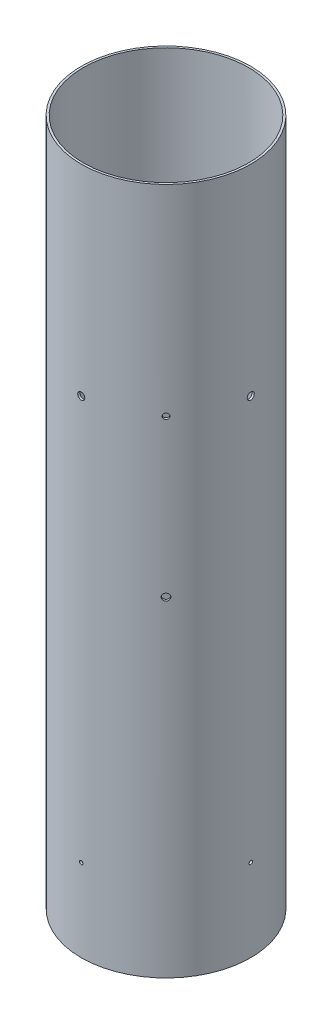
SolidWorks part; units mm, degrees
ref_plane "Front Plane" through (0, 0, 0) normal (0, 0, 1) x (1, 0, 0)
ref_plane "Top Plane" through (0, 0, 0) normal (0, 1, 0) x (1, 0, 0)
ref_plane "Right Plane" through (0, 0, 0) normal (1, 0, 0) x (0, 0, -1)
sketch "Sketch2" plane through (0, 0, 0) normal (0, 1, 0) x (1, 0, 0)
  circle A0 centre (0, 0) radius 76.3651
  circle A1 centre (0, 0) radius 78.359
  dimension "D1" = 152.7302
  dimension "D2" = 156.718
extrude "Boss-Extrude1" add sketch "Sketch2" along normal blind 635
ref_plane "Plane1" through (55.4082, 0, 55.4082) normal (0.7071, 0, 0.7071) x (0, -1, 0)
sketch "Sketch4" plane through (0, 0, 0) normal (0, 0, 1) x (1, 0, 0)
  circle A0 centre (0, 449.5038) radius 3.2639
  dimension "D2" = 6.5278
  dimension "D1" = 449.5038
extrude "Cut-Extrude2" cut sketch "Sketch4" against normal through all both and the other way through all
pattern_circular "CirPattern2" count 4 over 360 about axis through (0, 635, 0) along (0, 1, 0) of "Cut-Extrude2"
sketch "Sketch5" plane through (55.4082, 0, 55.4082) normal (0.7071, 0, 0.7071) x (0, -1, 0)
  circle A0 centre (-449.5038, 0) radius 2.5794
  dimension "D1" = 5.1587
  dimension "D2" = 449.5038
extrude "Cut-Extrude3" cut sketch "Sketch5" against normal up to surface and the other way through all up to face at (-76.299, 448.7564, 3.1772)
sketch "Sketch6" plane through (189.1754, 0, -78.359) normal (-0.7071, 0, -0.7071) x (-0.7071, 0, 0.7071)
  circle A0 centre (189.1754, 304.8) radius 3.175
  dimension "D2" = 304.8
extrude "Vent Hole" cut sketch "Sketch6" along normal up to surface (2.0599 mm away) up to face at (52.1938, 448.9122, 55.7444)
ref_plane "Plane2" through (0, 0, 78.359) normal (0, 0, 1) x (1, 0, 0)
sketch "Sketch7" plane through (0, 0, 78.359) normal (0, 0, 1) x (1, 0, 0)
  point P0 (0, 76.2)
  dimension "D1" = 76.2
hole_wizard "#4 Clearance Hole1" positions "Sketch7" profile "Sketch8" hole size "#4" standard "ANSI Inch" end condition through all
sketch "Sketch8" plane through (0, 76.2, 78.359) normal (1, 0, 0) x (0, -1, 0)
  line L0 (0, 0) -> (0, 156.718)
  line L1 (0, 156.718) -> (1.6319, 156.718)
  line L2 (1.6319, 156.718) -> (1.6319, 0)
  line L5 (1.6319, 0) -> (0, 0)
  line L11 (0, -6.35) -> (0, 107.95) construction
  dimension "Thru Hole Dia." = 3.2639
  dimension "Thru Hole Depth" = 156.718
pattern_circular "CirPattern3" count 2 every 90 about axis through (0, 0, 0) along (0, 1, 0) of "#4 Clearance Hole1"
equation "\"Shear Pin Dia\"= 3 / 32"
equation "\"Shear Pin Offset\"= 3"
equation "\"Bulkhead Screw Dia\"= 0.257"
equation "\"Bulkhead Screw Offset\"= 17.697"
equation "\"D1@Sketch4\"=\"Bulkhead Screw Offset\""
equation "\"D2@Sketch4\"=\"Bulkhead Screw Dia\""
equation "\"Rail Button Offset\"= 17.697"
equation "\"Rail Button Dia\"=0.2031"
equation "\"D1@Sketch5\"=\"Rail Button Dia\""
equation "\"Vent Hole Dia\"= 0.25"
equation "\"Vent Hole Offset\"= 12"
equation "\"D2@Sketch6\"=\"Vent Hole Offset\""
equation "\"D1@Sketch7\"=\"Shear Pin Offset\""
